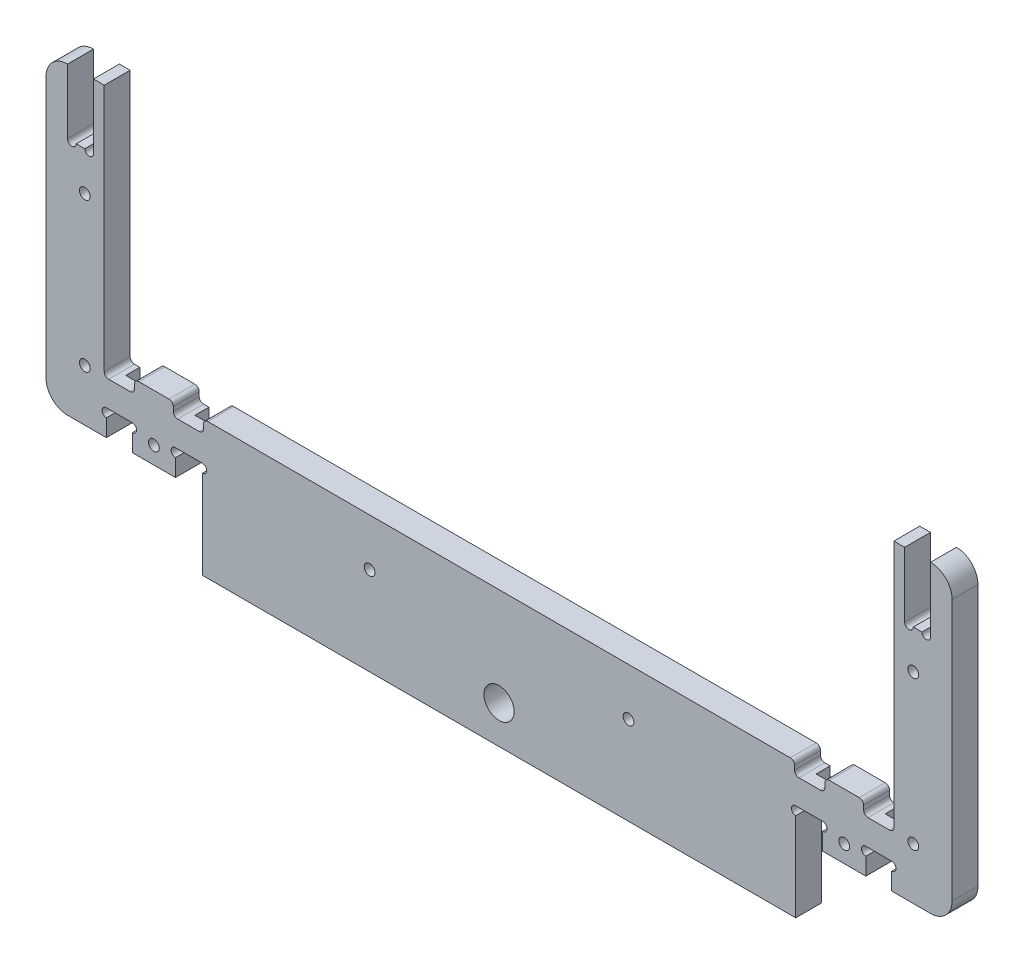
SolidWorks part; units mm, degrees
material "HDPE-green"
ref_plane "Front Plane" through (0, 0, 0) normal (0, 0, 1) x (1, 0, 0)
ref_plane "Top Plane" through (0, 0, 0) normal (0, 1, 0) x (1, 0, 0)
ref_plane "Right Plane" through (0, 0, 0) normal (1, 0, 0) x (0, 0, -1)
sketch "Sketch1" plane through (0, 0, 0) normal (0, 0, 1) x (1, 0, 0)
  line L1 (-137.5, -16.5) -> (137.5, -16.5)
  line L2 (-137.5, -16.5) -> (-137.5, 16.5)
  line L3 (-137.5, 16.5) -> (137.5, 16.5)
  line L4 (137.5, -16.5) -> (137.5, 16.5)
  line L5 (-137.5, -16.5) -> (137.5, 16.5) construction
  line L6 (-137.5, 16.5) -> (137.5, -16.5) construction
  point P0 (0, 0)
  dimension "D1" = 275
  dimension "D2" = 33
extrude "Boss-Extrude1" add sketch "Sketch1" along normal blind 12
sketch "Sketch2" plane through (0, 0, 12) normal (0, 0, 1) x (1, 0, 0)
  line L0 (137.5, 16.5) -> (-137.5, 16.5) construction
  line L1 (-16.5, 1) -> (20.0379, 1) construction
  circle A0 centre (0, 1) radius 7
  point P2 (0, 16.5)
  dimension "D1" = 15.5
  dimension "D2" = 14
extrude "Cut-Extrude1" cut sketch "Sketch2" against normal up to next
sketch "Sketch3" plane through (0, 0, 12) normal (0, 0, 1) x (1, 0, 0)
  line L1 (-210, 16.5) -> (210, 16.5)
  line L2 (-210, 16.5) -> (-210, 157.5)
  line L3 (-183, 46.5) -> (183, 46.5)
  line L4 (210, 16.5) -> (210, 157.5)
  line L5 (-210, 157.5) -> (-183, 157.5)
  line L8 (-183, 46.5) -> (-183, 157.5)
  line L9 (183, 157.5) -> (210, 157.5)
  line L13 (183, 46.5) -> (183, 157.5)
  circle A0 centre (0, 1) radius 7 construction
  dimension "D1" = 30
  dimension "D3" = 210
  dimension "D8" = 111
extrude "Boss-Extrude2" add sketch "Sketch3" against normal blind 12
sketch "Sketch5" plane through (0, 0, 12) normal (0, 0, 1) x (1, 0, 0)
  line L0 (-183, 46.5) -> (-183, 40.5)
  line L1 (-183, 40.5) -> (-169, 40.5)
  line L2 (-169, 40.5) -> (-169, 46.5)
  line L3 (183, 46.5) -> (-183, 46.5) construction
  line L4 (-169, 46.5) -> (-183, 46.5)
  line L5 (-151, 46.5) -> (-151, 40.5)
  line L6 (-151, 40.5) -> (-137, 40.5)
  line L7 (-137, 40.5) -> (-137, 46.5)
  line L8 (-151, 46.5) -> (-137, 46.5)
  circle A0 centre (0, 1) radius 7 construction
  dimension "D1" = 14
  dimension "D2" = 6
  dimension "D3" = 6
  dimension "D4" = 14
  dimension "D5" = 137
  dimension "D6" = 169
extrude "Cut-Extrude3" cut sketch "Sketch5" against normal up to next
fillet "Fillet1" radius 2 7 edges at (-137, 40.5, 6) (-151, 40.5, 6) (-169, 40.5, 6) (-183, 40.5, 6) (-169, 46.5, 6) (-151, 46.5, 6) (-137, 46.5, 6)
sketch "Sketch17" plane through (0, 0, 0) normal (0, 0, -1) x (-1, 0, 0)
  line L1 (149, 40.5) -> (139, 40.5) construction
  line L2 (141.5, 52.5) -> (146.5, 52.5)
  line L3 (141.5, 52.5) -> (141.5, 28.5)
  line L4 (141.5, 28.5) -> (146.5, 28.5)
  line L5 (146.5, 52.5) -> (146.5, 28.5)
  line L6 (141.5, 52.5) -> (146.5, 28.5) construction
  line L9 (181, 40.5) -> (171, 40.5) construction
  line L10 (178.5, 28.5) -> (173.5, 28.5)
  line L11 (178.5, 28.5) -> (178.5, 52.5)
  line L12 (178.5, 52.5) -> (173.5, 52.5)
  line L13 (173.5, 28.5) -> (173.5, 52.5)
  line L14 (178.5, 28.5) -> (173.5, 52.5) construction
  line L15 (178.5, 52.5) -> (173.5, 28.5) construction
  line L16 (141.5, 28.5) -> (146.5, 52.5) construction
  point P0 (144, 40.5)
  point P7 (176, 40.5)
  dimension "D1" = 5
  dimension "D2" = 24
  dimension "D3" = 5
  dimension "D4" = 24
extrude "Cut-Extrude9" cut sketch "Sketch17" against normal blind 6.5
sketch "Sketch6" plane through (0, 0, 12) normal (0, 0, 1) x (1, 0, 0)
  line L0 (-183, 157.5) -> (-210, 157.5) construction
  line L1 (-200, 157.5) -> (-188, 157.5)
  line L2 (-200, 157.5) -> (-200, 127.5)
  line L3 (-200, 127.5) -> (-188, 127.5)
  line L4 (-188, 157.5) -> (-188, 127.5)
  line L5 (-210, 157.5) -> (-210, 16.5) construction
  dimension "D1" = 12
  dimension "D2" = 10
  dimension "D3" = 30
extrude "Cut-Extrude4" cut sketch "Sketch6" against normal up to next
mirror "Mirror3" about plane through (0, 0, 0) normal (1, 0, 0) of "Cut-Extrude4"
hole_wizard "Ø5.0 (5) Diameter Hole2" positions "Sketch8" profile "Sketch7" hole size "Ø5.0" standard "ISO" end condition up to next
sketch "Sketch8" plane through (0, 0, 12) normal (0, 0, 1) x (1, 0, 0)
  line L0 (-210, 16.5) -> (-137.5, 16.5) construction
  line L2 (-183, 42.5) -> (-183, 157.5) construction
  line L3 (-183, 42.5) -> (-183, 157.5) construction
  point P0 (-192, 40.5)
  point P9 (-192, 109.5)
  dimension "D1" = 24
  dimension "D2" = 9
  dimension "D3" = 93
  dimension "D4" = 9
sketch "Sketch7" plane through (-192, 40.5, 12) normal (1, 0, 0) x (0, -1, 0)
  line L0 (0, 0) -> (0, 12.0011)
  line L1 (0, 12.0011) -> (2.5, 12.0011)
  line L2 (2.5, 12.0011) -> (2.5, 0)
  line L5 (2.5, 0) -> (0, 0)
  line L11 (0, -6.35) -> (0, 107.95) construction
  dimension "Thru Hole Dia." = 5
  dimension "Thru Hole Depth" = 12.0011
mirror "Mirror4" about plane through (0, 0, 0) normal (1, 0, 0) of "Ø5.0 (5) Diameter Hole2"
hole_wizard "Ø5.0 (5) Diameter Hole1" positions "Sketch10" profile "Sketch9" hole size "Ø5.0" standard "ISO"
sketch "Sketch10" plane through (0, 0, 12) normal (0, 0, 1) x (1, 0, 0)
  line L0 (-137.5, -16.5) -> (137.5, -16.5) construction
  circle A0 centre (0, 1) radius 7 construction
  point P1 (-60, 24.5)
  point P3 (60, 24.5)
  point P16 (-160, 24.5)
  point P18 (160, 24.5)
  dimension "D2" = 41
  dimension "D3" = 41
  dimension "D4" = 41
  dimension "D5" = 60
  dimension "D6" = 60
  dimension "D7" = 41
  dimension "D9" = 160
  dimension "D10" = 160
sketch "Sketch9" plane through (-60, 24.5, 12) normal (1, 0, 0) x (0, -1, 0)
  line L0 (0, 0) -> (0, 13.5022)
  line L1 (0, 13.5022) -> (2.5, 12)
  line L2 (2.5, 12) -> (2.5, 0)
  line L5 (2.5, 0) -> (0, 0)
  line L10 (0, 13.5022) -> (-2.5, 12) construction
  line L11 (0, -6.35) -> (0, 107.95) construction
  dimension "Hole Dia." = 5
  dimension "Hole Depth" = 12
  dimension "Drill Angle" = 118
fillet "Fillet2" radius 10 4 edges at (210, 157.5, 6) (210, 16.5, 6) (-210, 16.5, 6) (-210, 157.5, 6)
sketch "Sketch11" plane through (0, 0, 0) normal (0, 0, -1) x (-1, 0, 0)
  line L0 (-200, 127.5) -> (-188, 127.5) construction
  line L1 (200, 127.5) -> (188, 127.5) construction
  line L2 (-200, 127.5) -> (-196, 127.5)
  line L3 (-192, 127.5) -> (-188, 127.5)
  line L4 (188, 127.5) -> (192, 127.5)
  line L5 (196, 127.5) -> (200, 127.5)
  arc A0 (-200, 127.5) -> (-196, 127.5) centre (-198, 127.5) ccw
  arc A1 (-188, 127.5) -> (-192, 127.5) centre (-190, 127.5) cw
  arc A2 (188, 127.5) -> (192, 127.5) centre (190, 127.5) ccw
  arc A3 (200, 127.5) -> (196, 127.5) centre (198, 127.5) cw
  dimension "D1" = 2
  dimension "D2" = 2
  dimension "D3" = 2
  dimension "D4" = 2
extrude "Cut-Extrude5" cut sketch "Sketch11" against normal up to next
sketch "Sketch18" plane through (0, 0, 0) normal (0, 0, -1) x (-1, 0, 0)
  line L0 (200, 16.5) -> (137.5, 16.5) construction
  line L1 (150, 16.5) -> (137.5, 16.5)
  line L2 (150, 16.5) -> (150, 24.5)
  line L3 (150, 28.5) -> (137.5, 28.5)
  line L4 (137.5, 16.5) -> (137.5, 24.5)
  line L5 (149, 40.5) -> (139, 40.5) construction
  line L6 (181, 40.5) -> (171, 40.5) construction
  line L7 (170, 16.5) -> (182, 16.5)
  line L8 (170, 16.5) -> (170, 24.5)
  line L9 (170, 28.5) -> (182, 28.5)
  line L10 (182, 16.5) -> (182, 24.5)
  arc A0 (150, 24.5) -> (150, 28.5) centre (150, 26.5) ccw
  arc A1 (170, 28.5) -> (170, 24.5) centre (170, 26.5) ccw
  arc A2 (137.5, 28.5) -> (137.5, 24.5) centre (137.5, 26.5) ccw
  arc A3 (182, 24.5) -> (182, 28.5) centre (182, 26.5) ccw
  point P13 (176, 40.5)
  point P17 (144, 40.5)
  dimension "D7" = 4
  dimension "D8" = 4
  dimension "D9" = 4
  dimension "D10" = 4
  dimension "D1" = 12.5
  dimension "D2" = 6
  dimension "D3" = 12
  dimension "D4" = 12
  dimension "D5" = 12
  dimension "D6" = 6
extrude "Cut-Extrude10" cut sketch "Sketch18" against normal up to next
mirror "Mirror2" about plane through (0, 0, 0) normal (1, 0, 0) of "Cut-Extrude10", "Fillet1", "Cut-Extrude3", "Cut-Extrude9"
